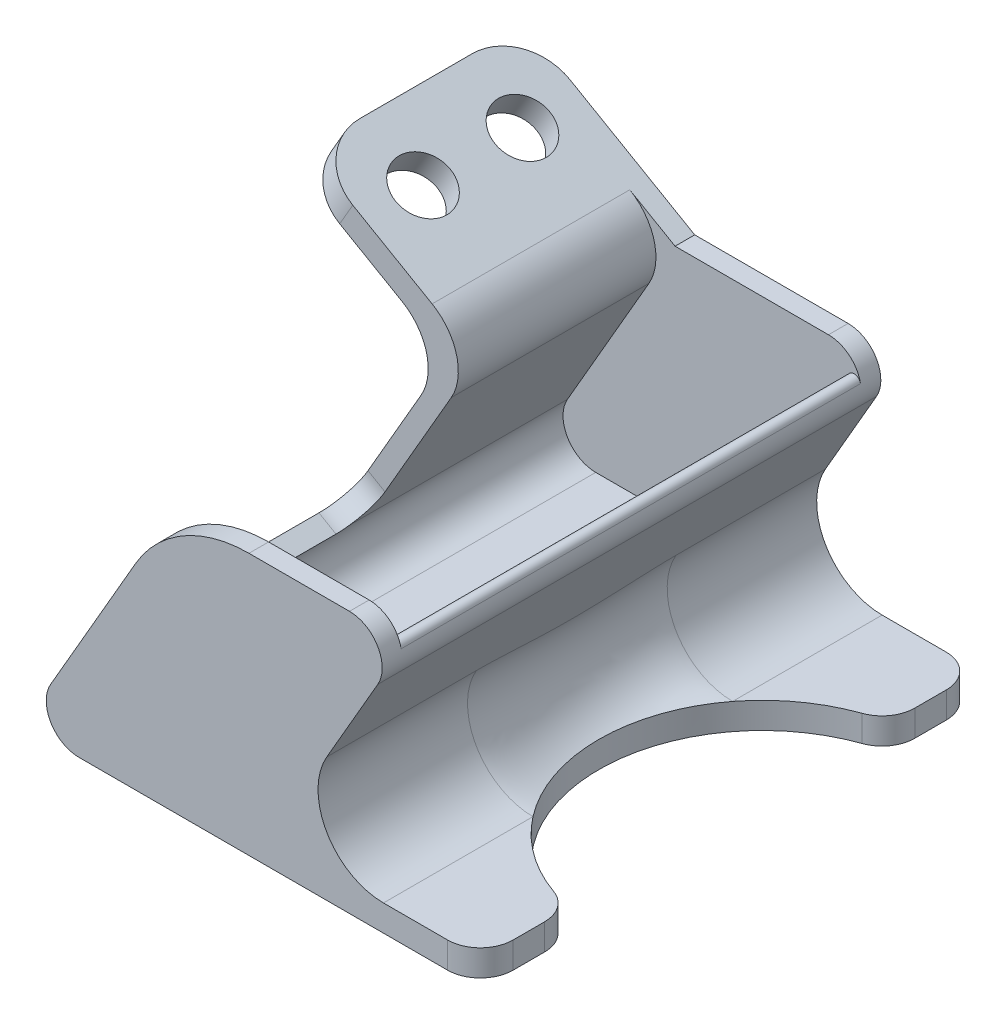
SolidWorks part; units mm, degrees
ref_plane "Front Plane" through (0, 0, 0) normal (0, 0, 1) x (1, 0, 0)
ref_plane "Top Plane" through (0, 0, 0) normal (0, 1, 0) x (1, 0, 0)
ref_plane "Right Plane" through (0, 0, 0) normal (1, 0, 0) x (0, 0, -1)
sketch "Sketch1" plane through (0, 0, 0) normal (0, 0, 1) x (1, 0, 0)
  line L0 (0, 0) -> (70, 0)
  line L1 (70, 0) -> (70, 4)
  line L2 (70, 4) -> (37.8742, 4)
  line L3 (37.8742, 4) -> (58.6588, 40)
  line L4 (58.6588, 40) -> (23.094, 40)
  line L5 (23.094, 40) -> (0, 0)
  dimension "D1" = 60
  dimension "D2" = 30.8
  dimension "D3" = 4
  dimension "D4" = 40
  dimension "D5" = 70
extrude "Boss-Extrude1" add sketch "Sketch1" along normal blind 76.2
sketch "Sketch2" plane through (0, 0, 0) normal (0, 0, -1) x (-1, 0, 0)
  line L0 (-26.5581, 40) -> (-5.7735, 4)
  line L1 (-58.6588, 40) -> (-23.094, 40) construction
  line L2 (-5.7735, 4) -> (-34.4101, 4)
  line L3 (-34.4101, 4) -> (-55.1947, 40)
  line L4 (-55.1947, 40) -> (-40.8322, 68.4113)
  line L5 (-40.8322, 68.4113) -> (-26.5581, 40)
  line L6 (-23.094, 40) -> (0, 0) construction
  line L7 (-37.8742, 4) -> (-58.6588, 40) construction
  point P11 (0, 0)
  dimension "D1" = 3
  dimension "D2" = 3
extrude "Cut-Extrude1" cut sketch "Sketch2" against normal blind 70.2 from offset 3 offset against normal yes
sketch "Sketch3" plane through (0, 0, 0) normal (0, -1, 0) x (1, 0, 0)
  line L0 (70, 76.2) -> (70, 0) construction
  circle A0 centre (75, 38.1) radius 25
  point P4 (70, 38.1)
  point P5 (0, 0)
  dimension "D1" = 50
  dimension "D2" = 5
extrude "Cut-Extrude2" cut sketch "Sketch3" against normal up to surface (4 mm away) up to face at (53.9371, 4, 38.1)
fillet "Fillet1" radius 10 1 edges at (37.8742, 4, 38.1)
fillet "Fillet2" radius 5 4 edges at (70, 2, 76.2) (70, 2, 62.5949) (70, 2, 13.6051) (70, 2, 0)
fillet "Fillet3" radius 5 1 edges at (0, 0, 38.1)
fillet "Fillet4" radius 5 1 edges at (5.7735, 4, 38.1)
sketch "Sketch4" plane through (0, 0, 0) normal (-0.866, 0.5, 0) x (0, 0, 1)
  line L0 (0, 8.6603) -> (76.2, 8.6603) construction
  line L1 (73.2, 47.9201) -> (33.2, 47.9201)
  line L2 (73.2, 47.9201) -> (73.2, 14.6603)
  line L3 (73.2, 14.6603) -> (33.2, 14.6603)
  line L4 (33.2, 47.9201) -> (33.2, 14.6603)
  dimension "D1" = 6
  dimension "D2" = 40
extrude "Cut-Extrude3" cut sketch "Sketch4" against normal blind 8.2
fillet "Fillet6" radius 5 2 edges at (8.6345, 11.9431, 73.2) (8.6345, 11.9431, 33.2)
fillet "Fillet7" radius 20 1 edges at (23.094, 40, 74.7)
sketch "Sketch5" plane through (0, 0, 33.2) normal (0, 0, 1) x (1, 0, 0)
  line L0 (26.5581, 40) -> (0.5774, 55)
  line L1 (0.5774, 55) -> (-1.4226, 51.5359)
  line L2 (-1.4226, 51.5359) -> (21.96, 38.0359)
  line L3 (23.094, 40) -> (9.8301, 17.0263) construction
  line L4 (21.96, 38.0359) -> (26.5581, 40)
  line L5 (46.5344, 19) -> (58.6588, 40) construction
  point P3 (-0.6701, 52.5946)
  dimension "D1" = 4
  dimension "D2" = 30
extrude "Boss-Extrude2" add sketch "Sketch5" against normal up to surface (33.2 mm away) up to face at (39.9971, 13.8438, 0)
sketch "Sketch6" plane through (7.3301, 12.6962, 0) normal (0.5, 0.866, 0) x (0.866, -0.5, 0)
  line L0 (30.8, 0) -> (3, 0) construction
  line L1 (-27, -33.2) -> (3, -33.2) construction
  line L2 (-27, 0) -> (-27, -33.2) construction
  circle A0 centre (-17, -9) radius 4.2
  circle A1 centre (-17, -24.2) radius 4.2
  dimension "D1" = 8.4
  dimension "D2" = 8.4
  dimension "D3" = 9
  dimension "D4" = 9
  dimension "D5" = 10
  dimension "D6" = 10
extrude "Cut-Extrude4" cut sketch "Sketch6" along normal blind 60.2
fillet "Fillet8" radius 8 2 edges at (-0.4226, 53.2679, 33.2) (-0.4226, 53.2679, 0)
fillet "Fillet9" radius 8 2 edges at (26.5581, 40, 18.1) (21.96, 38.0359, 16.6)
fillet "Fillet10" radius 5 1 edges at (58.6588, 40, 38.1)
fillet "Fillet12" radius 1 1 edges at (54.0219, 37.9686, 38.1)
